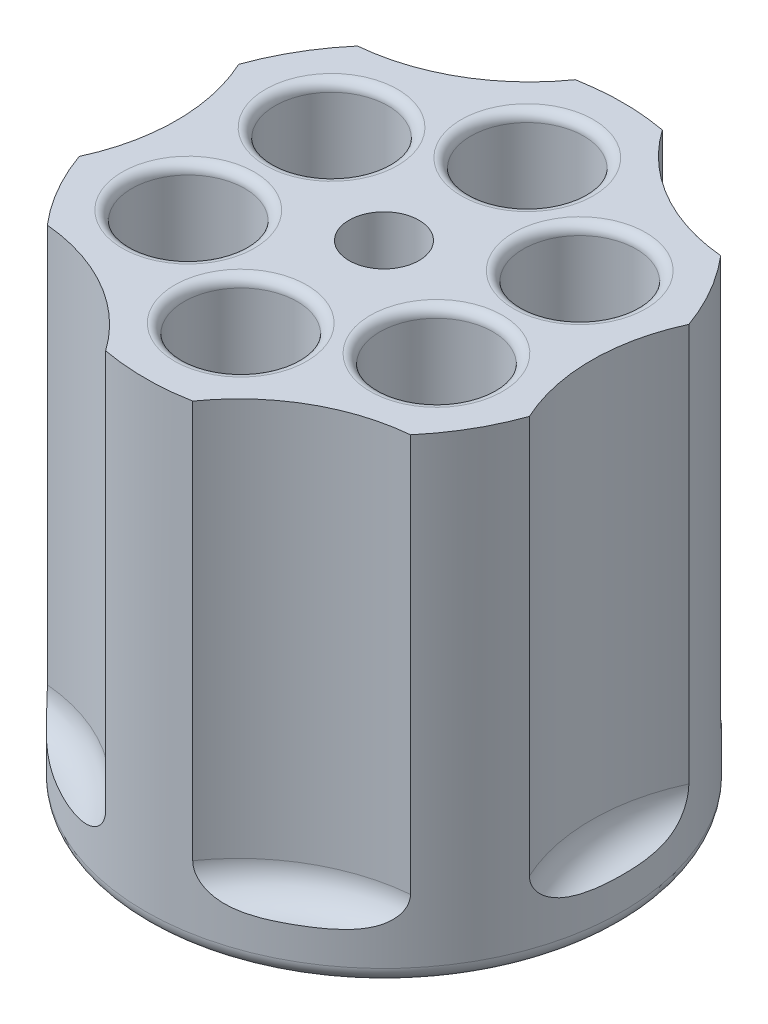
SolidWorks part; units mm, degrees
ref_plane "Front Plane" through (0, 0, 0) normal (0, 0, 1) x (1, 0, 0)
ref_plane "Top Plane" through (0, 0, 0) normal (0, 1, 0) x (1, 0, 0)
ref_plane "Right Plane" through (0, 0, 0) normal (1, 0, 0) x (0, 0, -1)
sketch "Sketch4" plane through (0, 0, 0) normal (0, 1, 0) x (1, 0, 0)
  circle A0 centre (0, 0) radius 19.05
  circle A1 centre (0, 0) radius 2.794
  point P7 (0, 0)
  point P20 (0, 0)
  dimension "D1" = 38.1
  dimension "D2" = 5.588
extrude "bullet_holes" add sketch "Sketch4" along normal blind 38.1
sketch "Sketch5" plane through (0, 38.1, 0) normal (0, 1, 0) x (1, 0, 0)
  line L0 (0, 0) -> (19.05, 0) construction
  line L1 (19.05, 0) -> (31.6925, 0) construction
  line L2 (0, 0) -> (9.8987, 5.715) construction
  circle A0 centre (0, 0) radius 19.05 construction
  arc A1 (17.9578, 6.3577) -> (17.9578, -6.3577) centre (31.6925, 0) ccw
  arc A2 (17.9578, 6.3577) -> (17.9578, -6.3577) centre (0, 0) cw
  circle A3 centre (9.8987, 5.715) radius 4.5085
  circle M6 centre (0, 0) radius 19.05
  dimension "D1" = 30
  dimension "D2" = 9.017
  dimension "D3" = 11.43
extrude "cool_cylinder_thing" cut sketch "Sketch5" against normal blind 34.29 contours A1 M6 | A3 region at (17.8329, 38.1, 0) region at (9.8987, 38.1, -5.715)
fillet "Fillet5" radius 0.762 1 edges at (9.8987, 38.1, -1.2065)
fillet "Fillet3" radius 2.54 1 edges at (16.5577, 3.81, 0)
pattern_circular "CirPattern2" count 6 over 360 about axis through (0, 38.1, 0) along (0, 1, 0) of "cool_cylinder_thing", "Fillet3", "Fillet5"
fillet "Fillet4" radius 1.27 1 edges at (0, 0, 19.05)
